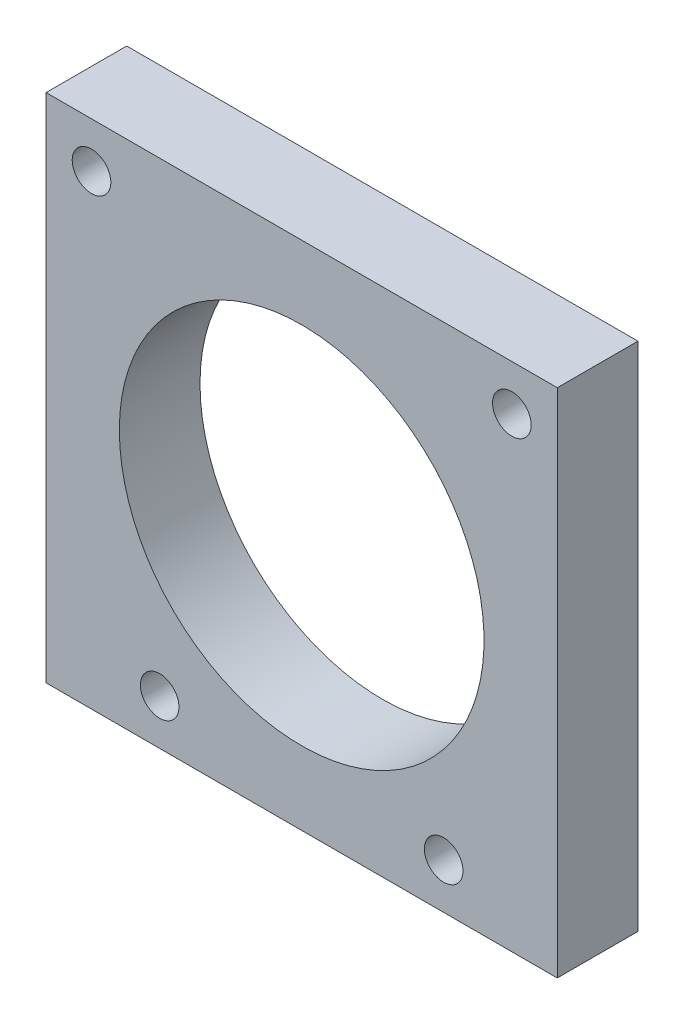
SolidWorks part; units mm, degrees
ref_plane "Front Plane" through (0, 0, 0) normal (0, 0, 1) x (1, 0, 0)
ref_plane "Top Plane" through (0, 0, 0) normal (0, 1, 0) x (1, 0, 0)
ref_plane "Right Plane" through (0, 0, 0) normal (1, 0, 0) x (0, 0, -1)
sketch "Sketch1" plane through (0, 0, 0) normal (0, 0, 1) x (1, 0, 0)
  line L1 (-22.5, -22.5) -> (22.5, -22.5)
  line L2 (-22.5, -22.5) -> (-22.5, 22.5)
  line L3 (-22.5, 22.5) -> (22.5, 22.5)
  line L4 (22.5, -22.5) -> (22.5, 22.5)
  line L5 (-22.5, -22.5) -> (22.5, 22.5) construction
  line L6 (-22.5, 22.5) -> (22.5, -22.5) construction
  circle A0 centre (0, 0) radius 16
  point P0 (0, 0)
  dimension "D3" = 32
  dimension "D1" = 45
  dimension "D2" = 45
extrude "Boss-Extrude1" add sketch "Sketch1" along normal blind 7.1
hole_wizard "M3x0.5 Tapped Hole1" positions "Sketch2" profile "Sketch3" tap size "M3x0.5" standard "ANSI Metric"
sketch "Sketch2" plane through (0, 0, 0) normal (0, 0, -1) x (-1, 0, 0)
  line L16 (-18.5, 18.5) -> (-18.5, -18.5)
  line L17 (-18.5, -18.5) -> (18.5, -18.5)
  line L18 (18.5, -18.5) -> (18.5, 18.5)
  line L19 (18.5, 18.5) -> (-18.5, 18.5)
  point P25 (-18.5, 18.5)
  point P28 (18.5, 18.5)
  point P104 (-12.5, -18.5)
  point P106 (12.5, -18.5)
  dimension "D2" = 6
  dimension "D3" = 6
sketch "Sketch3" plane through (18.5, 18.5, 0) normal (1, 0, 0) x (0, 1, 0)
  line L0 (0, 0) -> (0, 15.7511)
  line L1 (0, 15.7511) -> (1.25, 15)
  line L2 (1.25, 15) -> (1.25, 0)
  line L3 (1.25, 0) -> (0, 0)
  line L4 (0, 15.7511) -> (-1.25, 15) construction
  line L5 (0, -6.35) -> (0, 107.95) construction
  dimension "Tap Drill Dia." = 2.5
  dimension "Tap Drill Depth" = 15
  dimension "Drill Angle" = 118
hole_wizard "CBORE for M3 SHCS1" positions "Sketch4" profile "Sketch5" counterbore size "M3" standard "ANSI Metric"
sketch "Sketch4" plane through (0, 0, 0) normal (0, 0, -1) x (-1, 0, 0)
  point P0 (-18.5, 18.5)
  point P3 (18.5, 18.5)
  point P6 (12.5, -18.5)
  point P9 (-12.5, -18.5)
sketch "Sketch5" plane through (18.5, 18.5, 0) normal (1, 0, 0) x (0, 1, 0)
  line L0 (0, 0) -> (0, 8.1215)
  line L1 (0, 8.1215) -> (1.7, 7.1)
  line L2 (1.7, 7.1) -> (1.7, 3)
  line L3 (1.7, 3) -> (3.25, 3)
  line L4 (3.25, 3) -> (3.25, 0)
  line L5 (3.25, 0) -> (0, 0)
  line L6 (0, 8.1215) -> (-1.7, 7.1) construction
  line L7 (0, -6.35) -> (0, 107.95) construction
  dimension "Hole Dia." = 3.4
  dimension "Hole Depth" = 7.1
  dimension "C'Bore Dia." = 6.5
  dimension "C'Bore Depth" = 3
  dimension "Drill Angle" = 118
other "3D Printing Tolerance" flip direction yes face at (16, 0, 7.1) offset 0.05 parameters "D1"=0.05
